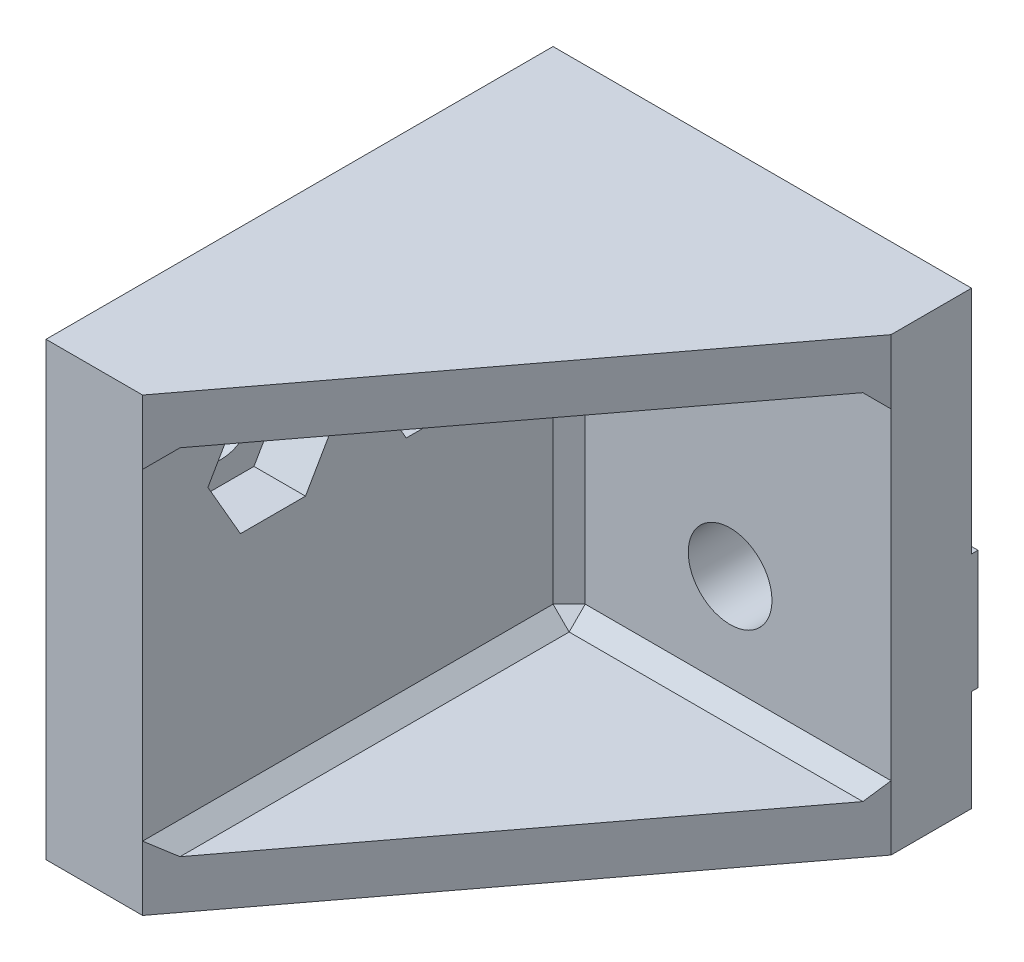
SolidWorks part; units mm, degrees
ref_plane "Спереди" through (0, 0, 0) normal (0, 0, 1) x (1, 0, 0)
ref_plane "Сверху" through (0, 0, 0) normal (0, 1, 0) x (1, 0, 0)
ref_plane "Справа" through (0, 0, 0) normal (1, 0, 0) x (0, 0, -1)
sketch "Эскиз1" plane through (0, 0, 0) normal (0, 0, 1) x (1, 0, 0)
  line L1 (0, -14) -> (20, -14)
  line L2 (0, -14) -> (0, 14)
  line L3 (0, 14) -> (20, 14)
  line L4 (20, -14) -> (20, 14)
  point P4 (0, 0)
  dimension "D1" = 28
  dimension "D2" = 20
extrude "Бобышка-Вытянуть1" add sketch "Эскиз1" along normal blind 5
sketch "Эскиз2" plane through (0, 0, 0) normal (0, 0, 1) x (1, 0, 0)
  line L1 (0, 14) -> (-6, 14)
  line L2 (0, 14) -> (0, -14)
  line L3 (0, -14) -> (-6, -14)
  line L4 (-6, 14) -> (-6, -14)
  dimension "D1" = 28
  dimension "D2" = 6
extrude "Бобышка-Вытянуть2" add sketch "Эскиз2" along normal blind 31.5
sketch "Эскиз7" plane through (0, 0, 0) normal (0, 0, -1) x (-1, 0, 0)
  line L1 (-20, 7.7) -> (6, 7.7)
  line L2 (-20, 7.7) -> (-20, 0.3)
  line L3 (-20, 0.3) -> (6, 0.3)
  line L4 (6, 7.7) -> (6, 0.3)
  line L6 (-20, -14) -> (-20, 14) construction
  line L7 (6, 14) -> (6, -14) construction
  line L8 (-20, 14) -> (6, 14) construction
  point P8 (-20, 4)
  dimension "D1" = 7.4
  dimension "D2" = 26
  dimension "D3" = 10
extrude "Бобышка-Вытянуть4" add sketch "Эскиз7" along normal blind 0.4
sketch "Эскиз3" plane through (-6, 0, 0) normal (-1, 0, 0) x (0, 0, 1)
  line L0 (31.5, -14) -> (0, -14) construction
  line L1 (31.5, 14) -> (5, 14) construction
  circle A0 centre (23.4, -7) radius 2.1
  circle A1 centre (13.1, -7) radius 2.1
  point P9 (18.25, 14)
  dimension "D1" = 4.2
  dimension "D2" = 4.2
  dimension "D3" = 10.3
  dimension "D4" = 7
  dimension "D5" = 5.15
  dimension "D6" = 5.15
extrude "Вырез-Вытянуть1" cut sketch "Эскиз3" against normal through all
sketch "Эскиз4" plane through (0, 0, 5) normal (0, 0, 1) x (1, 0, 0)
  line L0 (20, -14) -> (20, 14) construction
  line L2 (20, 14) -> (0, 14) construction
  circle A0 centre (10, 4) radius 2.6
  dimension "D1" = 5.2
  dimension "D2" = 10
  dimension "D3" = 10
extrude "Вырез-Вытянуть2" cut sketch "Эскиз4" against normal through all
sketch "Эскиз5" plane through (0, 0, 0) normal (1, 0, 0) x (0, 0, -1)
  line L1 (-19.3585, -7) -> (-21.3793, -3.5)
  line L2 (-21.3793, -3.5) -> (-25.4207, -3.5)
  line L3 (-25.4207, -3.5) -> (-27.4415, -7)
  line L4 (-27.4415, -7) -> (-25.4207, -10.5)
  line L5 (-25.4207, -10.5) -> (-21.3793, -10.5)
  line L6 (-21.3793, -10.5) -> (-19.3585, -7)
  line L7 (-9.0585, -7) -> (-11.0793, -3.5)
  line L8 (-11.0793, -3.5) -> (-15.1207, -3.5)
  line L9 (-15.1207, -3.5) -> (-17.1415, -7)
  line L10 (-17.1415, -7) -> (-15.1207, -10.5)
  line L11 (-15.1207, -10.5) -> (-11.0793, -10.5)
  line L12 (-11.0793, -10.5) -> (-9.0585, -7)
  circle A0 centre (-23.4, -7) radius 3.5 construction
  circle A1 centre (-13.1, -7) radius 3.5 construction
  dimension "D1" = 7
  dimension "D2" = 7
extrude "Вырез-Вытянуть3" cut sketch "Эскиз5" against normal blind 3.2
sketch "Эскиз6" plane through (0, 14, 0) normal (0, 1, 0) x (1, 0, 0)
  line L0 (0, -31.5) -> (20, -5)
  line L1 (20, -5) -> (0, -5)
  line L2 (0, -5) -> (0, -31.5)
extrude "Бобышка-Вытянуть3" add sketch "Эскиз6" against normal blind 3
mirror "Зеркальное отражение1" about plane through (0, 0, 0) normal (0, 1, 0) of "Бобышка-Вытянуть3"
chamfer "Фаска1" distance 1 angle 45 5 edges at (0, -11, 18.25) (10, -11, 5) (0, 0, 5) (10, 11, 5) (0, 11, 18.25)
mirror "Зеркальное отражение2" about plane through (0, 0, 0) normal (0, 1, 0) of bodies 109
delete or keep bodies "Тело-Удалить/Сохранить 1" type delete bodies bodies 109
